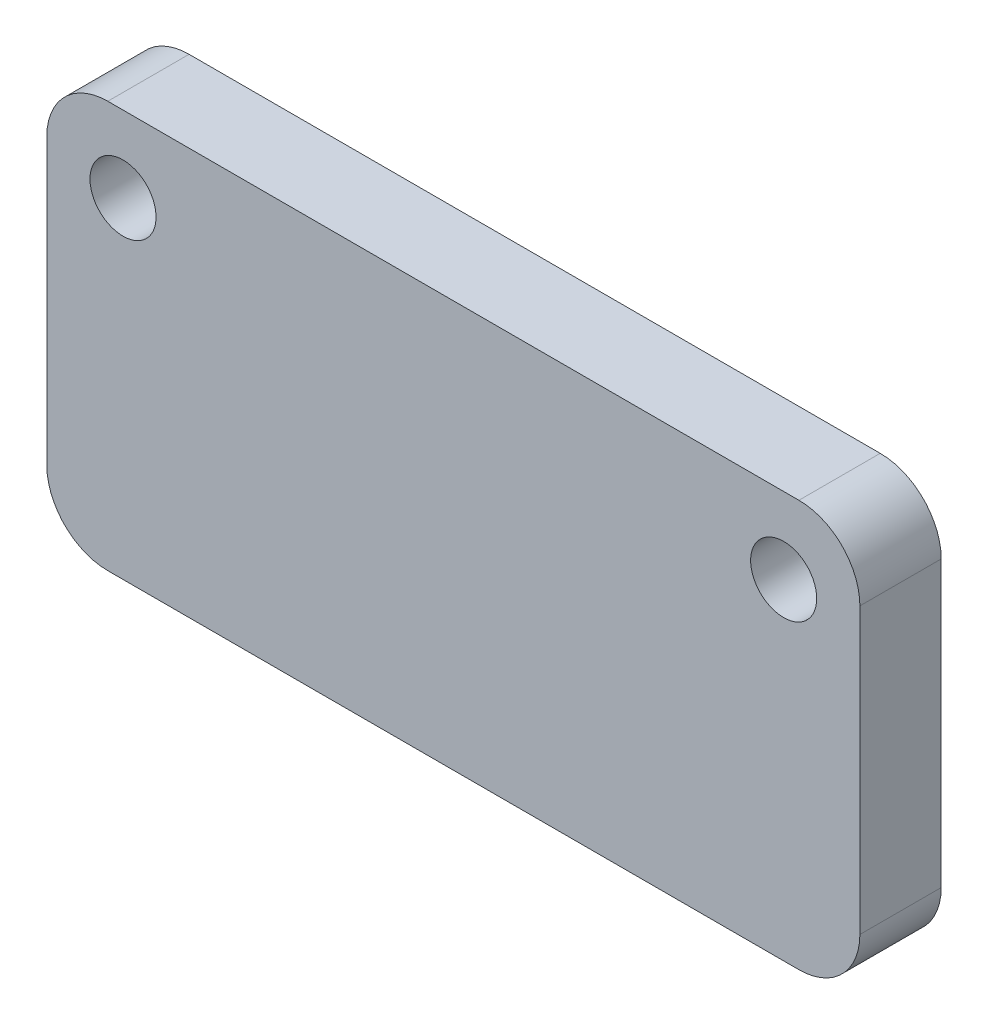
SolidWorks part; units mm, degrees
ref_plane "Front Plane" through (0, 0, 0) normal (0, 0, 1) x (1, 0, 0)
ref_plane "Top Plane" through (0, 0, 0) normal (0, 1, 0) x (1, 0, 0)
ref_plane "Right Plane" through (0, 0, 0) normal (1, 0, 0) x (0, 0, -1)
sketch "Sketch2" plane through (0, 0, 0) normal (0, 0, 1) x (1, 0, 0)
  line L0 (0, 0) -> (20, 0)
  line L1 (20, 0) -> (20, 20)
  line L2 (20, 20) -> (-20, 20)
  line L3 (-20, 20) -> (-20, 0)
  line L4 (-20, 0) -> (0, 0)
  line L5 (0, 0) -> (0, 20) construction
  line L6 (0, 16.25) -> (20, 16.25) construction
  circle A0 centre (16.25, 16.25) radius 1.625
  circle A1 centre (-16.25, 16.25) radius 1.625
  point P11 (16.2756, 3.75)
  dimension "D3" = 3.25
  dimension "D1" = 40
  dimension "D2" = 20
  dimension "D4" = 3.75
  dimension "D5" = 3.75
extrude "Boss-Extrude1" add sketch "Sketch2" along normal blind 4
fillet "Fillet1" radius 3 4 edges at (20, 0, 2) (20, 20, 2) (-20, 0, 2) (-20, 20, 2)
equation "\"D5@Sketch2\"=\"D4@Sketch2\""
